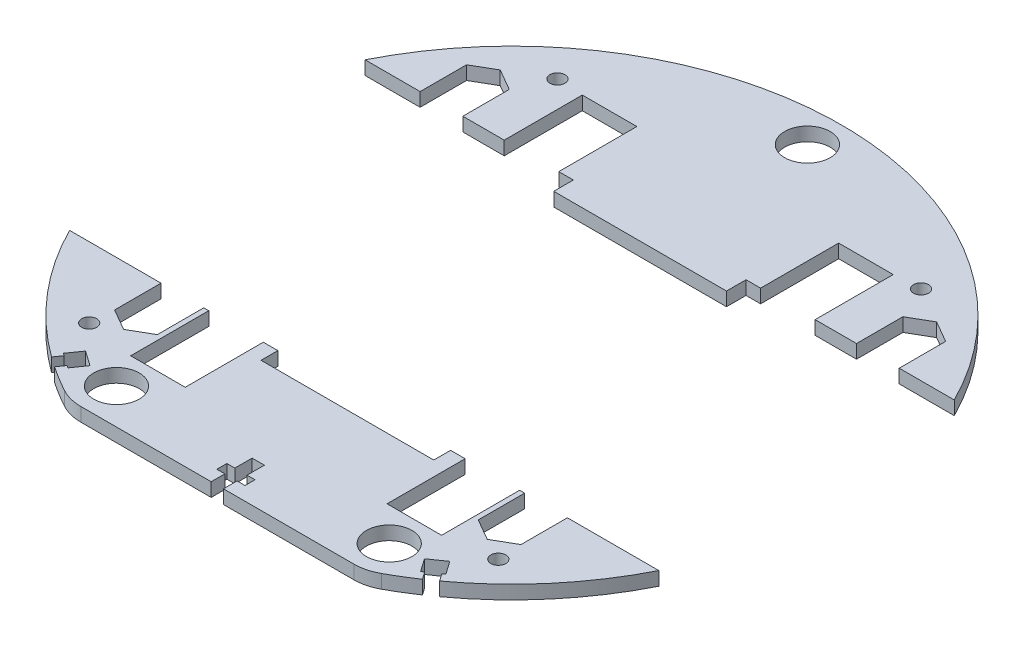
SolidWorks part; units mm, degrees
ref_plane "Front Plane" through (0, 0, 0) normal (0, 0, 1) x (1, 0, 0)
ref_plane "Top Plane" through (0, 0, 0) normal (0, 1, 0) x (1, 0, 0)
ref_plane "Right Plane" through (0, 0, 0) normal (1, 0, 0) x (0, 0, -1)
sketch "Sketch1" plane through (0, 0, 0) normal (0, 1, 0) x (1, 0, 0)
  line L0 (-30.03, -64.8129) -> (30.03, -64.8129)
  line L1 (0, -85) -> (0, 0) construction
  line L2 (0, -85) -> (32.4891, -64.8129) construction
  arc A0 (34.8348, -63.5829) -> (-34.8348, -63.5829) centre (0, 0) ccw
  circle A1 centre (0, -85) radius 38.25 construction
  arc A2 (30.03, -64.8129) -> (34.8348, -63.5829) centre (30.03, -54.8129) ccw
  arc A3 (-30.03, -64.8129) -> (-34.8348, -63.5829) centre (-30.03, -54.8129) cw
  dimension "D1" = 145
  dimension "D2" = 76.5
  dimension "D4" = 10
  dimension "D3" = 85
extrude "Boss-Extrude1" add sketch "Sketch1" along normal blind 3
sketch "Sketch2" plane through (0, 3, 0) normal (0, 1, 0) x (1, 0, 0)
  line L0 (18, -36.2) -> (-18, -36.2) construction
  line L1 (-34.2, -49.6757) -> (-22.2, -49.6757)
  line L2 (-34.2, -49.6757) -> (-34.2, 49.6757)
  line L3 (-34.2, 49.6757) -> (-22.2, 49.6757)
  line L4 (-22.2, -49.6757) -> (-22.2, -32.5)
  line L5 (-19, -32.5) -> (-22.2, -32.5) construction
  line L6 (-22.2, -49.6757) -> (-22.2, -32.5)
  line L7 (-19, -32.5) -> (-22.2, -32.5)
  line L8 (19, 28.2) -> (-19, 28.2) construction
  line L9 (18, -36.2) -> (-18, -36.2)
  line L10 (-19, 32.5) -> (-22.2, 32.5) construction
  line L11 (-19, 32.5) -> (-22.2, 32.5)
  line L12 (19, 28.2) -> (-19, 28.2)
  line L13 (-19, -32.5) -> (-19, -36.2)
  line L14 (-19, -36.2) -> (-18, -36.2)
  line L15 (-19, 32.5) -> (-19, 28.2)
  line L16 (-22.2, 32.5) -> (-22.2, 49.6757)
  line L17 (0, 0) -> (0, -64.8129) construction
  line L18 (-30.03, -64.8129) -> (30.03, -64.8129) construction
  line L19 (22.2, 32.5) -> (22.2, 49.6757)
  line L20 (19, 32.5) -> (19, 28.2)
  line L21 (19, -36.2) -> (18, -36.2)
  line L22 (19, -32.5) -> (19, -36.2)
  line L23 (19, 32.5) -> (22.2, 32.5)
  line L24 (19, -32.5) -> (22.2, -32.5)
  line L25 (22.2, -49.6757) -> (22.2, -32.5)
  line L26 (22.2, -49.6757) -> (22.2, -32.5)
  line L27 (34.2, 49.6757) -> (22.2, 49.6757)
  line L28 (34.2, -49.6757) -> (34.2, 49.6757)
  line L29 (34.2, -49.6757) -> (22.2, -49.6757)
extrude "Cut-Extrude1" cut sketch "Sketch2" against normal through all contours L29 L28 L27 L19 L23 L20 L12 L15 L11 L16 L3 L2 L1 L4 L7 L13 L14 L9 L21 L22 L24 L25 region at (0, 3, 1.8654)
sketch "Sketch3" plane through (0, 3, 0) normal (0, 1, 0) x (1, 0, 0)
  line L0 (-34.2, 32.5) -> (-34.2, -32.5)
  line L1 (-72.5, -32.5) -> (-34.2, -32.5)
  line L2 (-72.5, -32.5) -> (-72.5, 32.5)
  line L3 (-72.5, 32.5) -> (-34.2, 32.5)
  line L4 (72.5, -32.5) -> (72.5, 32.5)
  line L5 (-72.5, -32.5) -> (72.5, 32.5) construction
  line L6 (-72.5, 32.5) -> (72.5, -32.5) construction
  line L7 (-34.2, -49.6757) -> (-34.2, 49.6757) construction
  line L8 (34.2, 32.5) -> (34.2, -32.5)
  line L9 (34.2, -49.6757) -> (34.2, 49.6757) construction
  line L10 (34.2, 32.5) -> (72.5, 32.5)
  line L11 (34.2, -32.5) -> (72.5, -32.5)
  arc A0 (34.8348, -63.5829) -> (-34.8348, -63.5829) centre (0, 0) ccw construction
  point P0 (0, 0)
  dimension "D1" = 65
extrude "Cut-Extrude2" cut sketch "Sketch3" against normal through all
sketch "Sketch4" plane through (0, 3, 0) normal (0, 1, 0) x (1, 0, 0)
  line L0 (0, 0) -> (0, -20.7985) construction
  circle A0 centre (30, -57) radius 5
  circle A4 centre (-30, -57) radius 5
  dimension "D3" = 10
  dimension "D1" = 57
  dimension "D2" = 30
extrude "Cut-Extrude3" cut sketch "Sketch4" against normal through all
sketch "Sketch5" plane through (0, 3, 0) normal (0, 1, 0) x (1, 0, 0)
  line L0 (-52.7, 37.2865) -> (-52.7, 32.5)
  line L2 (-34.2, 32.5) -> (-64.8074, 32.5) construction
  line L3 (-52.7, 32.5) -> (-43.3, 32.5)
  line L4 (-43.3, 32.5) -> (-43.3, 37.2865)
  line L6 (-44.7, -37.2865) -> (-44.7, -32.5)
  line L7 (-64.8074, -32.5) -> (-34.2, -32.5) construction
  line L8 (0, 0) -> (0, -64.8129) construction
  line L9 (-30.03, -64.8129) -> (30.03, -64.8129) construction
  line L16 (-35.3, -37.2865) -> (-35.3, -32.5)
  line L17 (-43.3, 42.7135) -> (-48, 45.4271)
  line L18 (-48, 45.4271) -> (-52.7, 42.7135)
  line L19 (-52.7, 42.7135) -> (-52.7, 37.2865)
  line L20 (-52.7, 37.2865) -> (-48, 34.5729) construction
  line L21 (-48, 34.5729) -> (-43.3, 37.2865) construction
  line L22 (-43.3, 37.2865) -> (-43.3, 42.7135)
  line L23 (-40, -34.5729) -> (-44.7, -37.2865) construction
  line L24 (-44.7, -37.2865) -> (-44.7, -42.7135)
  line L25 (-44.7, -42.7135) -> (-40, -45.4271)
  line L26 (-40, -45.4271) -> (-35.3, -42.7135)
  line L27 (-35.3, -42.7135) -> (-35.3, -37.2865)
  line L28 (-35.3, -37.2865) -> (-40, -34.5729) construction
  line L30 (-35.3, -32.5) -> (-44.7, -32.5)
  line L31 (35.3, -37.2865) -> (40, -34.5729) construction
  line L32 (40, -34.5729) -> (44.7, -37.2865) construction
  line L33 (48, 34.5729) -> (43.3, 37.2865) construction
  line L34 (52.7, 37.2865) -> (48, 34.5729) construction
  line L35 (35.3, -32.5) -> (44.7, -32.5)
  line L36 (35.3, -42.7135) -> (35.3, -37.2865)
  line L37 (40, -45.4271) -> (35.3, -42.7135)
  line L38 (44.7, -42.7135) -> (40, -45.4271)
  line L39 (44.7, -37.2865) -> (44.7, -42.7135)
  line L40 (43.3, 37.2865) -> (43.3, 42.7135)
  line L41 (52.7, 42.7135) -> (52.7, 37.2865)
  line L42 (48, 45.4271) -> (52.7, 42.7135)
  line L43 (43.3, 42.7135) -> (48, 45.4271)
  line L44 (35.3, -37.2865) -> (35.3, -32.5)
  line L45 (44.7, -37.2865) -> (44.7, -32.5)
  line L46 (43.3, 32.5) -> (43.3, 37.2865)
  line L47 (52.7, 32.5) -> (43.3, 32.5)
  line L48 (52.7, 37.2865) -> (52.7, 32.5)
  circle A2 centre (-48, 40) radius 4.7 construction
  circle A3 centre (-40, -40) radius 4.7 construction
  circle A4 centre (40, -40) radius 4.7 construction
  circle A5 centre (48, 40) radius 4.7 construction
  dimension "D1" = 9.4
  dimension "D2" = 48
  dimension "D3" = 40
  dimension "D4" = 40
  dimension "D5" = 40
  dimension "D6" = 9.4
extrude "Cut-Extrude4" cut sketch "Sketch5" against normal through all
sketch "Sketch7" plane through (0, 3, 0) normal (0, 1, 0) x (1, 0, 0)
  line L0 (0, 0) -> (0, 65) construction
  circle A0 centre (0, 65) radius 5
  dimension "D1" = 10
  dimension "D2" = 65
extrude "Cut-Extrude6" cut sketch "Sketch7" against normal through all
sketch "Sketch8" plane through (0, 3, 0) normal (0, 1, 0) x (1, 0, 0)
  line L0 (-1.35, -64.8129) -> (-1.35, -61.8129)
  line L1 (-30.03, -64.8129) -> (30.03, -64.8129) construction
  line L2 (-1.35, -61.8129) -> (-3.1, -61.8129)
  line L3 (-3.1, -61.8129) -> (-3.1, -59.6129)
  line L4 (-3.1, -59.6129) -> (-1.35, -59.6129)
  line L5 (-1.35, -59.6129) -> (-1.35, -55.8129)
  line L6 (-1.35, -55.8129) -> (1.35, -55.8129)
  line L7 (1.35, -55.8129) -> (1.35, -59.6129)
  line L8 (1.35, -59.6129) -> (3.1, -59.6129)
  line L9 (3.1, -59.6129) -> (3.1, -61.8129)
  line L10 (3.1, -61.8129) -> (1.35, -61.8129)
  line L11 (1.35, -61.8129) -> (1.35, -64.8129)
  line L12 (-1.35, -64.8129) -> (1.35, -64.8129)
  line L13 (-30.03, -64.8129) -> (30.03, -64.8129) construction
  point P18 (0, -64.8129)
  point P19 (0, -64.8129)
  dimension "D1" = 2.7
  dimension "D2" = 2.2
  dimension "D3" = 6.2
  dimension "D5" = 9
extrude "Cut-Extrude7" cut sketch "Sketch8" against normal through all
sketch "Sketch9" plane through (0, 3, 0) normal (0, 1, 0) x (1, 0, 0)
  line L0 (0, 0) -> (0, -27.4582) construction
  circle A0 centre (45, -48) radius 1.65
  circle A1 centre (-45, -48) radius 1.65
  circle A2 centre (40, 50) radius 1.65
  circle A3 centre (-40, 50) radius 1.65
  dimension "D3" = 3.3
  dimension "D1" = 45
  dimension "D2" = 48
  dimension "D4" = 40
  dimension "D5" = 50
extrude "Cut-Extrude8" cut sketch "Sketch9" against normal through all
sketch "Sketch10" plane through (0, 3, 0) normal (0, 1, 0) x (1, 0, 0)
  line L0 (0, 0) -> (0, -36.2) construction
  line L1 (-19, -36.2) -> (19, -36.2) construction
  line L2 (0, 0) -> (41.5843, -59.3885) construction
  line L3 (36.7913, -56.0303) -> (40.0679, -53.736)
  line L4 (36.7913, -56.0303) -> (38.7988, -58.8974)
  line L5 (40.0679, -53.736) -> (42.0754, -56.6031)
  line L6 (38.7988, -58.8974) -> (39.3313, -58.5245)
  line L7 (39.3313, -58.5245) -> (40.4784, -60.1629)
  line L8 (40.4784, -60.1629) -> (42.6901, -58.6142)
  line L9 (42.6901, -58.6142) -> (41.543, -56.9759)
  line L10 (41.543, -56.9759) -> (42.0754, -56.6031)
  line L11 (-41.543, -56.9759) -> (-42.0754, -56.6031)
  line L12 (-42.6901, -58.6142) -> (-41.543, -56.9759)
  line L13 (-40.4784, -60.1629) -> (-42.6901, -58.6142)
  line L14 (-39.3313, -58.5245) -> (-40.4784, -60.1629)
  line L15 (-38.7988, -58.8974) -> (-39.3313, -58.5245)
  line L16 (-40.0679, -53.736) -> (-42.0754, -56.6031)
  line L17 (-36.7913, -56.0303) -> (-38.7988, -58.8974)
  line L18 (-36.7913, -56.0303) -> (-40.0679, -53.736)
  arc A0 (34.8348, -63.5829) -> (64.8074, -32.5) centre (0, 0) ccw construction
  point P5 (38.4296, -54.8832)
  point P18 (41.5843, -59.3885)
  dimension "D1" = 35
  dimension "D2" = 4
  dimension "D3" = 3.5
  dimension "D4" = 2.7
extrude "Cut-Extrude9" cut sketch "Sketch10" against normal through all
equation "\"smallPulleyTeeth\"= 30"
equation "\"largePulleyTeeth\"= 30"
equation "\"eighthThick\"= 3.0mm"
equation "\"sixteenthThick\" = 1.7mm"
equation "\"quarterThick\"=6.0mm"
equation "\"OD\" = 145mm"
equation "\"puckAngle\" = 60.5deg"
equation "\"puckDiam\" = 76.5mm"
equation "\"axlePress\" = 5.9mm"
equation "\"press\" = 0.2mm"
equation "\"wheelClear\" = 0.3mm"
equation "\"10-32clear\" = 4.8mm"
equation "\"6-32clear\" = 3.3mm"
equation "\"8-32clear\" = 4.0mm"
equation "\"4-40clear\" = 3.0mm"
equation "\"wheelHeight\" = 22mm"
equation "\"wheelWell\" = 65mm"
equation "\"D1@Sketch1\"=\"OD\""
equation "\"D1@Boss-Extrude1\"=\"eighthThick\""
equation "\"D2@Sketch1\"=\"puckDiam\""
equation "\"D1@Sketch3\"=\"wheelWell\""
equation "\"puckDist\" = 85mm"
equation "\"scoopFillet\" = 5mm"
equation "\"10-32tap\" = 4.45mm"
equation "\"ledSmall\" = 3.1mm"
equation "\"ledLarge\" = 4.2mm"
equation "\"ledLength\" = 4.2mm"
equation "\"D3@Sketch1\"=\"puckDist\""
equation "\"4-40close\" = 2.7mm"
equation "\"4-40nutThick\" = 2.2mm"
equation "\"4-40nutWidth\" = 6.2mm"
equation "\"D1@Sketch8\"=\"4-40close\""
equation "\"D3@Sketch8\"=\"4-40nutWidth\""
equation "\"D3@Sketch9\"=\"6-32clear\""
equation "\"4-40insertHeight\" = 3.5mm"
equation "\"4-40insert\" = 4mm"
equation "\"D2@Sketch10\"=\"4-40insert\""
equation "\"D3@Sketch10\"=\"4-40insertHeight\""
equation "\"D4@Sketch10\"=\"4-40close\""
